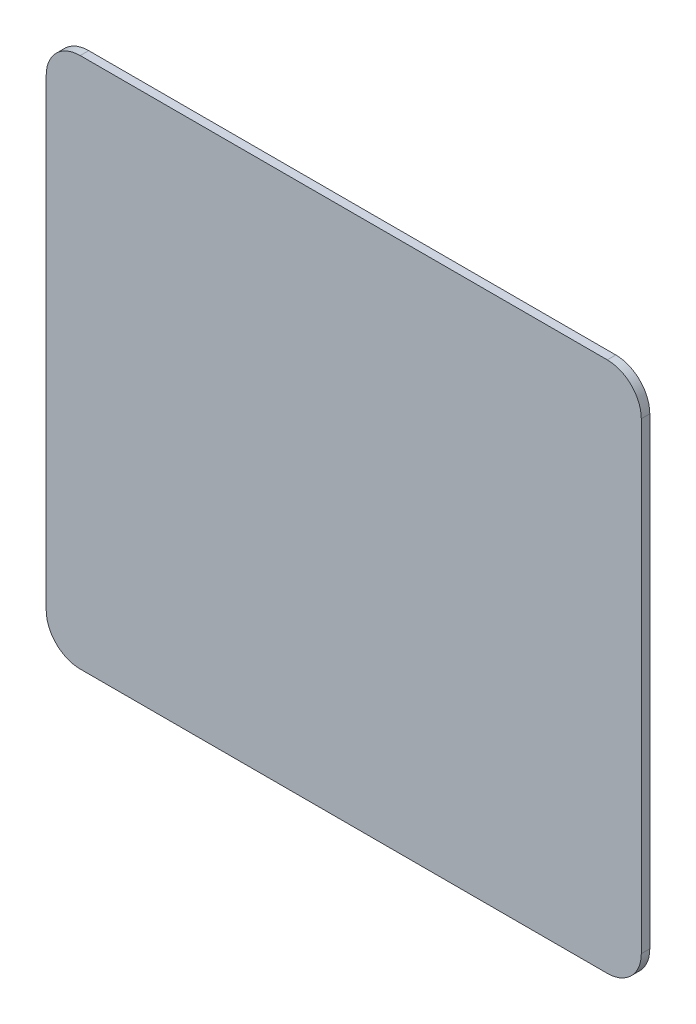
SolidWorks part; units mm, degrees
material "ABS PC"
ref_plane "Front Plane" through (0, 0, 0) normal (0, 0, 1) x (1, 0, 0)
ref_plane "Top Plane" through (0, 0, 0) normal (0, 1, 0) x (1, 0, 0)
ref_plane "Right Plane" through (0, 0, 0) normal (1, 0, 0) x (0, 0, -1)
sketch "Sketch1" plane through (0, 0, 0) normal (0, 0, 1) x (1, 0, 0)
  line L1 (-124, 125) -> (124, 125)
  line L2 (-140, 109) -> (-140, -109)
  line L3 (-124, -125) -> (124, -125)
  line L4 (140, 109) -> (140, -109)
  line L5 (-140, 125) -> (140, -125) construction
  line L6 (-140, -125) -> (140, 125) construction
  arc A0 (-140, -109) -> (-124, -125) centre (-124, -109) ccw
  arc A1 (124, -125) -> (140, -109) centre (124, -109) ccw
  arc A2 (124, 125) -> (140, 109) centre (124, 109) cw
  arc A3 (-124, 125) -> (-140, 109) centre (-124, 109) ccw
  point P0 (0, 0)
  dimension "D3" = 16
  dimension "D1" = 280
  dimension "D2" = 250
extrude "Boss-Extrude1" add sketch "Sketch1" along normal blind 4
